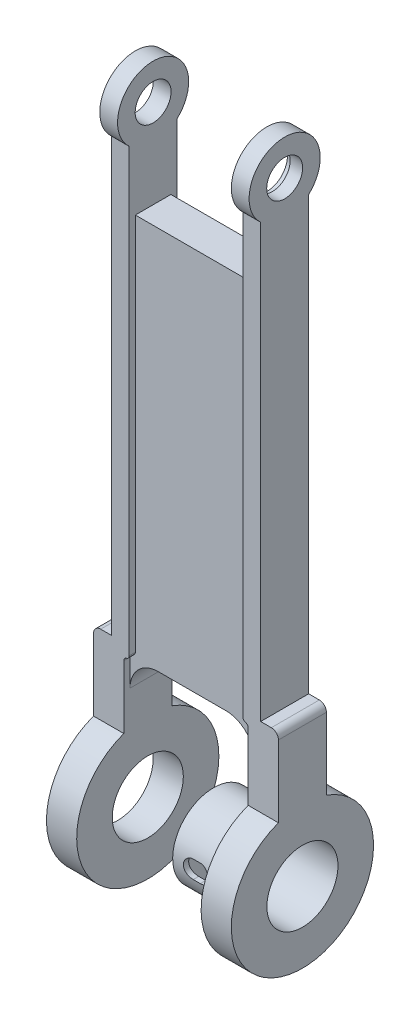
SolidWorks part; units mm, degrees
ref_plane "Alzado" through (0, 0, 0) normal (0, 0, 1) x (1, 0, 0)
ref_plane "Planta" through (0, 0, 0) normal (0, 1, 0) x (1, 0, 0)
ref_plane "Vista lateral" through (0, 0, 0) normal (1, 0, 0) x (0, 0, -1)
sketch "Croquis1" plane through (0, 0, 0) normal (0, 0, 1) x (1, 0, 0)
  line L0 (0, 0) -> (0, -143)
  line L1 (0, 0) -> (-1.6, 0)
  line L2 (-42, 0) -> (-42, -143)
  line L4 (-42, -35) -> (0, -35)
  line L5 (-42, -143) -> (0, -143)
  line L6 (-42, 0) -> (-37.4, 0)
  line L7 (-37.4, 0) -> (-37.4, -35)
  line L8 (-1.6, 0) -> (-1.6, -35)
  line L9 (-37.4, 0) -> (-42, 0)
  dimension "D1" = 42
extrude "Saliente-Extruir1" add sketch "Croquis1" against normal blind 10 contours L4 L5 region at (-21, -89, 0)
sketch "Croquis3" plane through (0, 0, 0) normal (0, 0, 1) x (1, 0, 0)
  line L0 (-47, -145) -> (-47, -160)
  line L1 (-47, -200) -> (-47, -180) construction
  line L2 (-47, -145) -> (-47, -141)
  line L4 (-47, -180) -> (-30.5, -180) construction
  line L5 (-42, -35) -> (-42, 0)
  line L6 (5, -143) -> (5, -200)
  line L7 (-47, -200) -> (-47, -180)
  line L8 (-30.5, -180) -> (-30.5, -143) construction
  line L9 (-42, -143) -> (0, -143) construction
  line L10 (-47, -180) -> (-47, -200)
  line L11 (-47, -180) -> (-47, -160)
  line L12 (-3.5, -151) -> (-3.5, -200)
  line L13 (-38.5, -200) -> (-38.5, -151)
  line L14 (5, -143) -> (5, -141)
  line L15 (-47, -200) -> (-38.5, -200)
  line L16 (-3.5, -200) -> (5, -200)
  line L17 (-45, -139) -> (-42, -139)
  line L18 (-42, -35) -> (-42, -143) construction
  line L19 (-30.5, -143) -> (-11.5, -143)
  line L20 (3, -139) -> (0, -139)
  line L21 (0, -35) -> (0, -143) construction
  line L22 (-30.5, -143) -> (-38.5, -143)
  line L23 (-38.5, -143) -> (-38.5, -151)
  line L24 (-30.5, -143) -> (-38.5, -143)
  arc A0 (5, -141) -> (3, -139) centre (3, -141) ccw
  arc A1 (-45, -139) -> (-47, -141) centre (-45, -141) ccw
  arc A2 (-11.5, -143) -> (-3.5, -151) centre (-11.5, -151) cw
  arc A3 (-38.5, -151) -> (-30.5, -143) centre (-30.5, -151) cw
  point P7 (5, -143)
  point P14 (10, -143)
  point P27 (-47, -143)
  point P29 (-49.26, -143)
  point P31 (7.26, -143)
  line M12 (-42, -35) -> (-42, -143)
  line M13 (-42, -143) -> (0, -143)
  line M14 (0, -143) -> (0, -35)
  dimension "D1" = 8.5
  dimension "D3" = 2
  dimension "D6" = 2
  dimension "D5" = 8
  dimension "D2" = 165
  dimension "D4" = 35
  dimension "D7" = 8.5
sketch "Croquis20" plane through (0, -35, 0) normal (0, 1, 0) x (1, 0, 0)
extrude "Saliente-Extruir2" add sketch "Croquis3" against normal blind 10 contours L17 A1 L2 L0 L11 L7 L15 L13 L23 M13 M12 | A2 L12 L16 L6 L14 A0 L20 M13 M14 region at (-42.813, -170.3435, 0) region at (0.6511, -169.665, 0)
sketch "Croquis21" plane through (0, 0, 0) normal (0, 0, 1) x (1, 0, 0)
  line L0 (-47, -145) -> (-47, -160)
  line L1 (-47, -200) -> (-47, -180) construction
  line L2 (-47, -145) -> (-47, -141)
  line L4 (-47, -180) -> (-30.5, -180) construction
  line L5 (-42, -35) -> (-42, 0)
  line L6 (5, -143) -> (5, -200)
  line L7 (-47, -200) -> (-47, -180)
  line L8 (-30.5, -180) -> (-30.5, -143) construction
  line L10 (-47, -180) -> (-47, -200)
  line L11 (-47, -180) -> (-47, -160)
  line L12 (-3.5, -151) -> (-3.5, -200)
  line L13 (-38.5, -200) -> (-38.5, -151)
  line L14 (5, -143) -> (5, -141)
  line L15 (-47, -200) -> (-38.5, -200)
  line L16 (-3.5, -200) -> (5, -200)
  line L17 (-45, -139) -> (-42, -139)
  line L19 (-30.5, -143) -> (-11.5, -143)
  line L20 (3, -139) -> (0, -139)
  line L22 (-30.5, -143) -> (-38.5, -143)
  line L23 (-38.5, -143) -> (-38.5, -151)
  line L24 (-30.5, -143) -> (-38.5, -143)
  arc A0 (5, -141) -> (3, -139) centre (3, -141) ccw
  arc A1 (-45, -139) -> (-47, -141) centre (-45, -141) ccw
  arc A2 (-11.5, -143) -> (-3.5, -151) centre (-11.5, -151) cw
  arc A3 (-38.5, -151) -> (-30.5, -143) centre (-30.5, -151) cw
  point P7 (5, -143)
  point P14 (10, -143)
  point P27 (-47, -143)
  point P29 (-49.26, -143)
  point P31 (7.26, -143)
  dimension "D1" = 8.5
  dimension "D3" = 2
  dimension "D6" = 2
  dimension "D5" = 8
  dimension "D4" = 35
  dimension "D7" = 8.5
extrude "Saliente-Extruir3" add sketch "Croquis21" against normal blind 10 contours L23 A3 L22 region at (-36.7131, -144.7869, 0)
sketch "Croquis22" plane through (0, 0, -10) normal (0, 0, -1) x (-1, 0, 0)
  line L0 (3.5, -156.8736) -> (3.5, -141.3338)
  line L1 (38.5, -155.5125) -> (38.5, -141.3338)
  line L2 (3.5, -151) -> (3.5, -200) construction
  line L3 (5, -139.3973) -> (5, -35)
  line L4 (42, -35) -> (0, -35) construction
  line L5 (0, -35) -> (0, -139) construction
  line L6 (5, -35) -> (0, -35)
  line L7 (38.5, -200) -> (38.5, -151) construction
  line L8 (37, -35) -> (37, -139.3973)
  line L9 (42, -35) -> (42, -139) construction
  line L10 (0, -35) -> (0, -139)
  line L11 (0, -139) -> (-3, -139)
  line L12 (45, -139) -> (42, -139) construction
  line L13 (47, -200) -> (47, -141) construction
  line L14 (47, -200) -> (38.5, -200) construction
  line L15 (3.5, -200) -> (-5, -200) construction
  line L16 (-5, -141) -> (-5, -200) construction
  line L17 (42, -35) -> (0, -35)
  line L18 (42, -35) -> (42, -139)
  line L19 (45, -139) -> (42, -139)
  line L20 (47, -200) -> (47, -141)
  line L21 (38.5, -200) -> (38.5, -151)
  line L22 (47, -200) -> (38.5, -200)
  line L23 (3.5, -200) -> (-5, -200)
  line L24 (-5, -141) -> (-5, -200)
  arc A0 (4.25, -140.3655) -> (3.5, -141.3338) centre (4.5, -141.3338) ccw
  arc A1 (4.25, -140.3655) -> (5, -139.3973) centre (4, -139.3973) ccw
  arc A2 (37.75, -140.3655) -> (37, -139.3973) centre (38, -139.3973) cw
  arc A3 (38.5, -141.3338) -> (37.75, -140.3655) centre (37.5, -141.3338) ccw
  arc A4 (47, -141) -> (45, -139) centre (45, -141) ccw construction
  arc A5 (-3, -139) -> (-5, -141) centre (-3, -141) ccw construction
  arc A6 (47, -141) -> (45, -139) centre (45, -141) ccw
  arc A7 (-3, -139) -> (-5, -141) centre (-3, -141) ccw
  line M10 (38.5, -151) -> (38.5, -200)
  line M11 (38.5, -200) -> (47, -200)
  line M12 (47, -200) -> (47, -141)
  arc M13 (47, -141) -> (45, -139) centre (45, -141) ccw
  line M14 (45, -139) -> (42, -139)
  line M15 (42, -139) -> (42, -35)
  line M16 (42, -35) -> (0, -35)
  line M17 (0, -35) -> (0, -139)
  line M18 (0, -139) -> (-3, -139)
  arc M19 (-3, -139) -> (-5, -141) centre (-3, -141) ccw
  line M20 (-5, -141) -> (-5, -200)
  line M21 (-5, -200) -> (3.5, -200)
  line M22 (3.5, -200) -> (3.5, -151)
  dimension "D2" = 1
  dimension "D3" = 1
  dimension "D5" = 1
  dimension "D6" = 1
  dimension "D1" = 5
  dimension "D4" = 5
extrude "Saliente-Extruir4" add sketch "Croquis22" along normal blind 1.75 contours A0 A1 L3 L0 M16 M17 M18 M19 M20 M21 M22 | A3 L1 L8 A2 M10 M11 M12 M13 M14 M15 M16 region at (-0.8883, -128.2038, -10) region at (-41.1117, -128.2038, -10)
sketch "Croquis24" plane through (0, 0, 0) normal (0, 0, 1) x (1, 0, 0)
  line L0 (-37, -35) -> (-37, -138.9269)
  line L1 (-42, -35) -> (0, -35) construction
  line L2 (-5, -35) -> (-5, -138.9269)
  line L3 (-42, -35) -> (-42, -139) construction
  line L4 (0, -35) -> (0, -139) construction
  line L5 (-38.5, -156.0308) -> (-38.5, -143.4351)
  line L6 (-38.5, -200) -> (-38.5, -151) construction
  line L7 (-3.5, -141.3338) -> (-3.5, -151) construction
  line L8 (-3.5, -151) -> (-3.5, -200) construction
  line L9 (-3.5, -151) -> (-3.5, -142.3338)
  line L10 (-37, -141.4986) -> (-37, -138.9269)
  line L11 (-5, -140.3973) -> (-5, -138.9269)
  line L12 (-3.5, -200) -> (5, -200) construction
  line L13 (5, -141) -> (5, -200) construction
  line L14 (3, -139) -> (0, -139) construction
  line L15 (-45, -139) -> (-42, -139) construction
  line L16 (-47, -200) -> (-47, -141) construction
  line L17 (-47, -200) -> (-38.5, -200) construction
  line L18 (-3.5, -151) -> (-3.5, -200)
  line L19 (-3.5, -200) -> (5, -200)
  line L20 (5, -141) -> (5, -200)
  line L21 (3, -139) -> (0, -139)
  line L22 (0, -35) -> (0, -139)
  line L23 (-42, -35) -> (-37, -35)
  line L24 (-42, -35) -> (-42, -139)
  line L25 (-45, -139) -> (-42, -139)
  line L26 (-47, -200) -> (-47, -141)
  line L27 (-47, -200) -> (-38.5, -200)
  line L28 (-38.5, -200) -> (-38.5, -151)
  line L29 (-5, -35) -> (0, -35)
  arc A0 (-4.25, -141.3655) -> (-5, -140.3973) centre (-4, -140.3973) cw
  arc A1 (-4.25, -141.3655) -> (-3.5, -142.3338) centre (-4.5, -142.3338) cw
  arc A2 (-37, -141.4986) -> (-37.75, -142.4669) centre (-38, -141.4986) cw
  arc A3 (-37.75, -142.4669) -> (-38.5, -143.4351) centre (-37.5, -143.4351) ccw
  arc A4 (5, -141) -> (3, -139) centre (3, -141) ccw construction
  arc A5 (-45, -139) -> (-47, -141) centre (-45, -141) ccw construction
  arc A6 (5, -141) -> (3, -139) centre (3, -141) ccw
  arc A7 (-45, -139) -> (-47, -141) centre (-45, -141) ccw
  point P28 (-37, -142.4986)
  line M6 (-3.5, -151) -> (-3.5, -200)
  line M7 (-3.5, -200) -> (5, -200)
  line M8 (5, -200) -> (5, -141)
  arc M9 (5, -141) -> (3, -139) centre (3, -141) ccw
  line M10 (3, -139) -> (0, -139)
  line M11 (0, -139) -> (0, -35)
  line M12 (0, -35) -> (-42, -35)
  line M13 (-42, -35) -> (-42, -139)
  line M14 (-42, -139) -> (-45, -139)
  arc M15 (-45, -139) -> (-47, -141) centre (-45, -141) ccw
  line M16 (-47, -141) -> (-47, -200)
  line M17 (-47, -200) -> (-38.5, -200)
  line M18 (-38.5, -200) -> (-38.5, -151)
  dimension "D3" = 1
  dimension "D4" = 1
  dimension "D5" = 1
  dimension "D6" = 1
  dimension "D1" = 5
  dimension "D2" = 5
extrude "Saliente-Extruir5" add sketch "Croquis24" along normal blind 1.75 contours A3 A2 L10 L0 L5 M12 M13 M14 M15 M16 M17 M18 | A0 A1 L9 L2 L11 M6 M7 M8 M9 M10 M11 M12 region at (-41.1016, -128.2438, 0) region at (-0.8931, -128.2221, 0)
ref_plane "Plano1" through (0, -35, 1.75) normal (0, 0, 1) x (1, 0, 0)
sketch "Croquis26" plane through (0, 0, 0) normal (0, 0, 1) x (1, 0, 0)
  line L4 (-42, -35) -> (-37, -35)
  line L5 (-42, -35) -> (-42, 0)
  line L6 (-42, 0) -> (-37, 0)
  line L7 (-37, -35) -> (-37, 0)
  line L8 (-5, -35) -> (0, -35)
  line L9 (-5, -35) -> (-5, 0)
  line L10 (-5, 0) -> (0, 0)
  line L11 (0, -35) -> (0, 0)
  dimension "D1" = 35
  dimension "D2" = 35
extrude "Saliente-Extruir6" add sketch "Croquis26" along normal up to surface (1.75 mm away) up to face at (-41.2164, -131.5986, 1.75)
sketch "Croquis27" plane through (0, 0, 0) normal (0, 0, -1) x (-1, 0, 0)
  line L1 (0, 0) -> (5, 0)
  line L2 (0, 0) -> (0, -35)
  line L3 (0, -35) -> (5, -35)
  line L4 (5, 0) -> (5, -35)
  line L5 (37, 0) -> (42, 0)
  line L6 (37, 0) -> (37, -35)
  line L7 (37, -35) -> (42, -35)
  line L8 (42, 0) -> (42, -35)
extrude "Saliente-Extruir7" add sketch "Croquis27" along normal up to surface (11.75 mm away) up to face at (-0.7836, -130.9682, -11.75)
sketch "Croquis28" plane through (-5, 0, 0) normal (-1, 0, 0) x (0, 0, 1)
  line L0 (-5, 0) -> (-5, -20) construction
  line L1 (1.75, 0) -> (-11.75, 0) construction
  line L2 (1.75, 0) -> (1.75, -140.3973) construction
  line L3 (1.75, 0) -> (1.75, -140.3973)
  line L4 (1.75, 0) -> (-11.75, 0)
  circle A0 centre (-5, -10) radius 10
  line M7 (1.75, -140.3973) -> (1.75, 0)
  line M8 (1.75, 0) -> (-11.75, 0)
  line M9 (-11.75, 0) -> (-11.75, -139.3973)
  dimension "D1" = 20
extrude "Cortar-Extruir3" cut sketch "Croquis28" against normal blind 99.75 and the other way through all contours A0 L4 M9 | A0 M7 M8 region at (-5, -0.7651, 0.1099) region at (-5, -0.7651, -10.1099)
extrude "Saliente-Extruir8" add sketch "Croquis28<5>" against normal up to surface (5 mm away) contours A0 M9 | L3 A0 region at (-5, -10, 3.07) region at (-5, -10, -13.07) up to face at (0, -70.1555, -5)
sketch "Croquis28<5>" plane through (-5, 0, 0) normal (-1, 0, 0) x (0, 0, 1) same geometry as "Croquis28"
sketch "Croquis29" plane through (-37, 0, 0) normal (1, 0, 0) x (0, 0, -1)
  line L0 (5, 0) -> (5, -20) construction
  arc A0 (11.75, -2.6218) -> (-1.75, -2.6218) centre (5, -10) ccw construction
  circle A1 centre (5, -10) radius 10
  dimension "D2" = 20
  dimension "D1" = 20
extrude "Saliente-Extruir9" add sketch "Croquis29" against normal up to surface (5 mm away) up to face at (-42, -70.1555, -5)
sketch "Croquis31" plane through (-38.5, 0, 0) normal (1, 0, 0) x (0, 0, -1)
  line L0 (5, -200) -> (5, -160) construction
  line L1 (11.75, -200) -> (-1.75, -200) construction
  line L2 (11.75, -200) -> (11.75, -141.3338) construction
  line L3 (-1.75, -200) -> (-1.75, -143.4351) construction
  line L4 (11.75, -198.8265) -> (11.75, -141.3338)
  line L5 (11.75, -200) -> (11.75, -141.3338)
  line L6 (-1.75, -198.8265) -> (-1.75, -143.4351)
  line L7 (11.75, -200) -> (-1.75, -200)
  line L8 (-1.75, -200) -> (-1.75, -143.4351)
  circle A0 centre (5, -180) radius 20
  line M5 (-1.75, -143.4351) -> (-1.75, -200)
  line M6 (-1.75, -200) -> (11.75, -200)
  line M7 (11.75, -200) -> (11.75, -141.3338)
  dimension "D2" = 40
  dimension "D1" = 40
extrude "Cortar-Extruir5" cut sketch "Croquis31" along normal through all both and the other way through all contours A0 M5 M6 | A0 L7 M7 region at (-38.5, -199.6498, -10.0726) region at (-38.5, -199.6498, 0.0726)
sketch "Croquis32" plane through (-38.5, 0, 0) normal (1, 0, 0) x (0, 0, -1)
  line L0 (5, -200) -> (5, -160) construction
  arc A0 (-1.75, -198.8265) -> (11.75, -198.8265) centre (5, -180) ccw construction
  circle A1 centre (5, -180) radius 20
  dimension "D1" = 40
extrude "Saliente-Extruir11" add sketch "Croquis32" against normal up to surface (8.5 mm away) up to face at (-47, -170.2066, -5)
sketch "Croquis33" plane through (-3.5, 0, 0) normal (-1, 0, 0) x (0, 0, 1)
  line L0 (-5, -200) -> (-5, -160) construction
  arc A0 (-11.75, -198.8265) -> (1.75, -198.8265) centre (-5, -180) ccw construction
  circle A1 centre (-5, -180) radius 20
  dimension "D1" = 40
extrude "Saliente-Extruir12" add sketch "Croquis33" against normal up to surface (8.5 mm away) up to face at (5, -170.2066, -5)
sketch "Croquis34" plane through (-42, 0, 0) normal (-1, 0, 0) x (0, 0, 1)
  circle A0 centre (-5, -10) radius 5.05
  dimension "D1" = 10.1
extrude "Cortar-Extruir6" cut sketch "Croquis34" against normal blind 90
sketch "Croquis39" plane through (-5, 0, 0) normal (-1, 0, 0) x (0, 0, 1)
  circle A0 centre (-5, -10) radius 5.78
  dimension "D1" = 11.56
extrude "Cortar-Extruir7" cut sketch "Croquis39" against normal blind 1.5
sketch "Croquis41" plane through (-38.5, 0, 0) normal (1, 0, 0) x (0, 0, -1)
  circle A0 centre (5, -180) radius 10
  dimension "D1" = 20
extrude "Cortar-Extruir8" cut sketch "Croquis41" against normal blind 43
sketch "Croquis42" plane through (5, 0, 0) normal (1, 0, 0) x (0, 0, -1)
  circle A0 centre (5, -180) radius 4
  dimension "D1" = 8
extrude "Cortar-Extruir9" cut sketch "Croquis42" against normal blind 27
sketch "Croquis43" plane through (5, 0, 0) normal (1, 0, 0) x (0, 0, -1)
  circle A0 centre (5, -180) radius 10
  dimension "D1" = 20
extrude "Cortar-Extruir10" cut sketch "Croquis43" against normal blind 12
sketch "Croquis45" plane through (-3.5, 0, 0) normal (-1, 0, 0) x (0, 0, 1)
  circle A0 centre (-5, -180) radius 11.5
  dimension "D1" = 23
extrude "Saliente-Extruir13" add sketch "Croquis45" along normal blind 16.5
fillet "Redondeo1" radius 2 1 edges at (-3.5, -191.5, -5)
sketch "Croquis48" plane through (-3.5, 0, 0) normal (1, 0, 0) x (0, 0, -1)
  circle A0 centre (5, -180) radius 10
extrude "Cortar-Extruir12" cut sketch "Croquis48" against normal blind 17
sketch "Croquis50" plane through (-20, 0, 0) normal (-1, 0, 0) x (0, 0, 1)
  line L0 (-5, -168.5) -> (-5, -180) construction
  line L1 (-5, -180) -> (-16.5, -180) construction
  line L2 (-16.5, -180) -> (-16.5, -183)
  line L3 (-16.5, -180) -> (-16.5, -176.344)
  line L4 (-16.5, -176.344) -> (-17.164, -176.344)
  line L5 (-17.164, -176.344) -> (-17.164, -183)
  line L6 (-17.164, -183) -> (-16.5, -183)
  line L7 (-16.5, -183) -> (-16.1018, -183)
  line L8 (-16.5, -176.344) -> (-15.9034, -176.344)
  circle A0 centre (-5, -180) radius 11.5 construction
  circle A1 centre (-5, -180) radius 11.5 construction
  circle A2 centre (-5, -180) radius 11.5
  circle M3 centre (-5, -180) radius 11.5
  dimension "D1" = 0.664
extrude "Saliente-Extruir16" add sketch "Croquis50" against normal blind 6 separate body contours L2 L7 M3 | L8 L3 M3 | L5 L6 L2 L3 L4 region at (-20, -182.2526, -16.3809) region at (-20, -179.672, -16.832) region at (-20, -177.2532, -16.3218)
sketch "Croquis52" plane through (-20, 0, 0) normal (-1, 0, 0) x (0, 0, 1)
  line L0 (-17.164, -183) -> (-16.1018, -183) construction
  line L1 (-15.9034, -176.344) -> (-17.164, -176.344) construction
  line L2 (-17.164, -176.344) -> (-17.164, -183) construction
  line L3 (-17.164, -183) -> (-16.1018, -183)
  line L4 (-15.9034, -176.344) -> (-17.164, -176.344)
  line L5 (-17.164, -176.344) -> (-17.164, -183)
  arc A0 (-15.9034, -176.344) -> (-16.1018, -183) centre (-5, -180) ccw construction
  arc A1 (-15.9034, -176.344) -> (-16.1018, -183) centre (-5, -180) ccw
extrude "Cortar-Extruir23" cut sketch "Croquis52" against normal blind 13
sketch "Croquis54" plane through (-20, 0, 0) normal (-1, 0, 0) x (0, 0, 1)
  circle A0 centre (-5, -180) radius 11.5
extrude "Saliente-Extruir17" add sketch "Croquis54" against normal up to surface (25 mm away) up to face at (5, -170, -5)
sketch "Croquis56" plane through (-20, 0, 0) normal (-1, 0, 0) x (0, 0, 1)
  circle A0 centre (-5, -180) radius 11.5 construction
  circle A1 centre (-5, -180) radius 11.5
sketch "Croquis57" plane through (5, 0, 0) normal (1, 0, 0) x (0, 0, -1)
  circle A1 centre (5, -180) radius 10
  dimension "D1" = 20
extrude "Cortar-Extruir26" cut sketch "Croquis57" against normal blind 23
sketch "Croquis58" plane through (-20, 0, 0) normal (-1, 0, 0) x (0, 0, 1)
  circle A0 centre (-5, -180) radius 4
  dimension "D1" = 8
extrude "Cortar-Extruir27" cut sketch "Croquis58" against normal blind 23
sketch "Croquis62" plane through (-20, 0, 0) normal (-1, 0, 0) x (0, 0, 1)
  line L0 (6.5, -180) -> (6.5, -177.5)
  line L1 (6.5, -180) -> (6.5, -182.5)
  line L2 (-5, -191.5) -> (-7.5, -191.5)
  line L3 (-5, -191.5) -> (-2.5, -191.5)
  line L4 (-7.5, -191.5) -> (-7.5, -194.143)
  line L5 (-7.5, -194.143) -> (-2.5, -194.143)
  line L6 (-2.5, -194.143) -> (-2.5, -191.5)
  line L7 (6.5, -182.5) -> (10.8223, -182.5)
  line L8 (10.8223, -182.5) -> (10.8223, -177.5)
  line L9 (10.8223, -177.5) -> (6.5, -177.5)
  circle A0 centre (-5, -180) radius 11.5
  dimension "D1" = 2.5
  dimension "D2" = 2.5
  dimension "D3" = 2.5
  dimension "D4" = 2.5
extrude "Saliente-Extruir18" add sketch "Croquis62" against normal blind 7.5 separate body contours L8 L9 L0 L1 L7 | L5 L6 L3 L2 L4 region at (-20, -180, 8.6612) region at (-20, -192.8215, -5)
sketch "Croquis63" plane through (0, -194.143, 0) normal (0, -1, 0) x (1, 0, 0)
  line L0 (-20, -5) -> (-17, -5) construction
  line L2 (-14.5, -5) -> (-12.5, -5) construction
  line L3 (-12.5, -7.5) -> (-12.5, -2.5) construction
  line L4 (-14.5, -2.5) -> (-12.5, -2.5)
  line L5 (-14.5, -7.5) -> (-12.5, -7.5)
  line L6 (-20, 6.5) -> (-20, -16.5) construction
  arc A0 (-14.5, -2.5) -> (-14.5, -7.5) centre (-14.5, -5) ccw
  arc A1 (-12.5, -7.5) -> (-12.5, -2.5) centre (-12.5, -5) ccw
  point P4 (-13.5, -5)
  dimension "D2" = 2
  dimension "D1" = 3
extrude "Cortar-Extruir28" cut sketch "Croquis63" against normal blind 7.5
sketch "Croquis64" plane through (0, -194.143, 0) normal (0, -1, 0) x (1, 0, 0)
  line L3 (-14.5, -2.5) -> (-20, -2.5)
  line L4 (-20, -2.5) -> (-20, -7.5)
  line L5 (-20, -7.5) -> (-14.5, -7.5)
  line L6 (-14.5, -2.5) -> (-20, -2.5)
  line L7 (-20, -2.5) -> (-20, -7.5)
  line L8 (-20, -7.5) -> (-14.5, -7.5)
  arc A1 (-14.5, -2.5) -> (-14.5, -7.5) centre (-14.5, -5) ccw
  arc A2 (-14.5, -2.5) -> (-14.5, -7.5) centre (-14.5, -5) ccw
  dimension "D1" = 0
extrude "Cortar-Extruir30" cut sketch "Croquis64" against normal up to surface (2.918 mm away) up to face at (-13.5, -191.361, -5)
sketch "Croquis65" plane through (0, 0, 10.8223) normal (0, 0, 1) x (1, 0, 0)
  line L5 (-20, -177.5) -> (-20, -182.5)
  line L6 (-20, -182.5) -> (-12.5, -182.5)
  line L7 (-12.5, -182.5) -> (-12.5, -177.5)
  line L8 (-12.5, -177.5) -> (-20, -177.5)
  line L9 (-20, -177.5) -> (-20, -182.5)
  line L10 (-20, -182.5) -> (-12.5, -182.5)
  line L11 (-12.5, -182.5) -> (-12.5, -177.5)
  line L12 (-12.5, -177.5) -> (-20, -177.5)
  line L13 (-14.5, -180) -> (-12.5, -180) construction
  line L15 (-14.5, -177.5) -> (-12.5, -177.5)
  line L16 (-14.5, -182.5) -> (-12.5, -182.5)
  arc A2 (-14.5, -177.5) -> (-14.5, -182.5) centre (-14.5, -180) ccw
  arc A3 (-12.5, -182.5) -> (-12.5, -177.5) centre (-12.5, -180) ccw
  point P2 (-20, -180)
  point P6 (-13.5, -180)
  point P12 (-17, -180)
  point P13 (-10, -180)
  line M9 (-12.5, -182.5) -> (-12.5, -177.5)
  line M10 (-12.5, -177.5) -> (-20, -177.5)
  dimension "D1" = 0
  dimension "D2" = 2.5
  dimension "D3" = 7
  dimension "D4" = 3
extrude "Cortar-Extruir33" cut sketch "Croquis65" against normal up to surface (6.1399 mm away) contours A3 L11 M9 | A2 L10 L11 M10 M9 region at (-14.521, -180, 10.8223) region at (-11.439, -180, 10.8223) up to face at (-13.5, -189.8396, -5)
sketch "Croquis67" plane through (0, 0, 10.8223) normal (0, 0, 1) x (1, 0, 0)
  line L3 (-14.5, -177.5) -> (-20, -177.5)
  line L4 (-20, -177.5) -> (-20, -182.5)
  line L5 (-20, -182.5) -> (-14.5, -182.5)
  line L6 (-14.5, -177.5) -> (-20, -177.5)
  line L7 (-20, -177.5) -> (-20, -182.5)
  line L9 (-20, -182.5) -> (-14.5, -182.5)
  arc A1 (-14.5, -177.5) -> (-14.5, -182.5) centre (-14.5, -180) ccw
  arc A3 (-14.5, -177.5) -> (-14.5, -182.5) centre (-14.5, -180) ccw
  dimension "D1" = 0
extrude "Cortar-Extruir34" cut sketch "Croquis67" against normal up to surface (4.5973 mm away) up to face at (-13.5, -180, 6.361)
